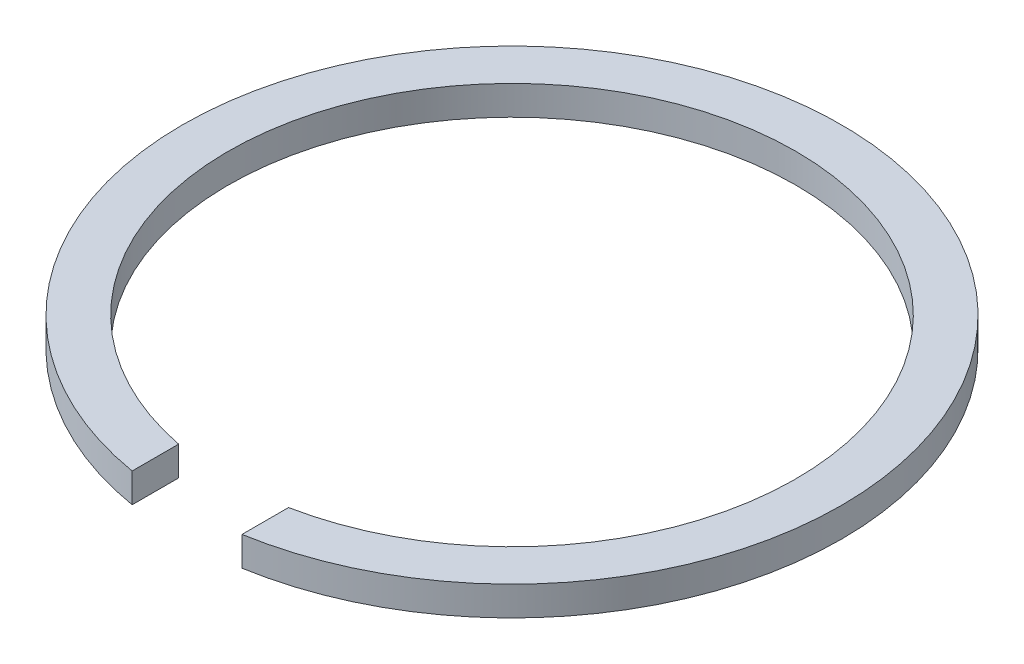
SolidWorks part; units mm, degrees
material "AISI 304"
ref_plane "Front Plane" through (0, 0, 0) normal (0, 0, 1) x (1, 0, 0)
ref_plane "Top Plane" through (0, 0, 0) normal (0, 1, 0) x (1, 0, 0)
ref_plane "Right Plane" through (0, 0, 0) normal (1, 0, 0) x (0, 0, -1)
sketch "Sketch1" plane through (0, 0, 0) normal (0, 1, 0) x (1, 0, 0)
  line L0 (0, 12.5) -> (0, -12.5) construction
  line L1 (1.5, -8.8741) -> (1.5, -7.6035)
  line L2 (-1.5, -8.8741) -> (-1.5, -7.6035)
  arc A0 (1.5, -8.8741) -> (-1.5, -8.8741) centre (0, 0) ccw
  arc A1 (1.5, -7.6035) -> (-1.5, -7.6035) centre (0, 0) ccw
  dimension "D1" = 18
  dimension "D2" = 15.5
  dimension "D3" = 3
  dimension "D4" = 25
  dimension "D5" = 1.5
extrude "Boss-Extrude1" add sketch "Sketch1" along normal blind 0.8 contours A1 L2 A0 L1
